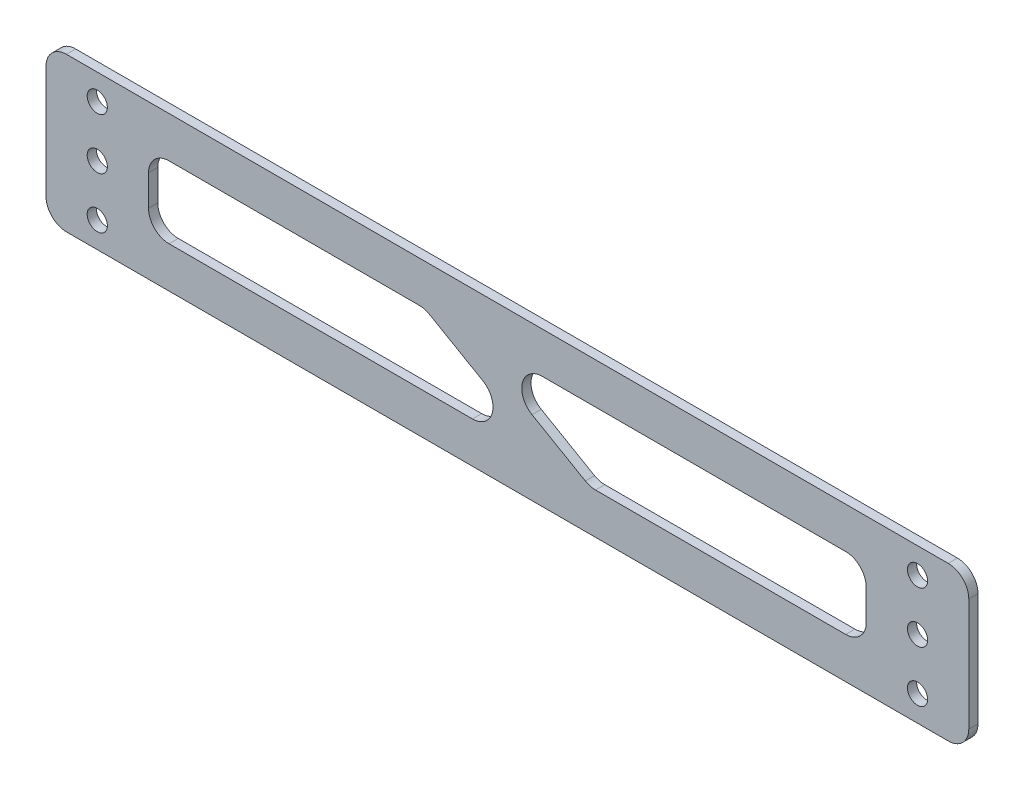
SolidWorks part; units mm, degrees
material "6061-T6 (SS)"
ref_plane "Front Plane" through (0, 0, 0) normal (0, 0, 1) x (1, 0, 0)
ref_plane "Top Plane" through (0, 0, 0) normal (0, 1, 0) x (1, 0, 0)
ref_plane "Right Plane" through (0, 0, 0) normal (1, 0, 0) x (0, 0, -1)
sketch "Sketch1" plane through (0, 0, 0) normal (0, 0, 1) x (1, 0, 0)
  line L1 (-12.7, 774.7) -> (49987.3, 774.7) construction
  line L2 (-7.62, 368.3) -> (210.82, 368.3) construction
  line L3 (-12.7, 1181.1) -> (-12.7, 368.3) construction
  line L4 (-7.62, 755.65) -> (210.82, 755.65)
  line L5 (-12.7, 760.73) -> (-12.7, 788.67)
  line L6 (-7.62, 793.75) -> (210.82, 793.75)
  line L7 (215.9, 760.73) -> (215.9, 788.67)
  line L8 (215.9, 1181.1) -> (215.9, 368.3) construction
  line L9 (17.78, 783.59) -> (79.7609, 783.59)
  line L10 (12.7, 1181.1) -> (12.7, 368.3) construction
  line L11 (190.5, 1181.1) -> (190.5, 368.3) construction
  line L12 (190.5, 778.51) -> (190.5, 770.89)
  line L13 (185.42, 765.81) -> (123.4391, 765.81)
  line L14 (12.7, 770.89) -> (12.7, 778.51)
  line L15 (82.3009, 782.9094) -> (95.4991, 775.2894)
  line L16 (107.7009, 774.1106) -> (120.8991, 766.4906)
  line L17 (81.1221, 783.59) -> (81.1221, -49216.41) construction
  line L18 (122.0779, 765.81) -> (122.0779, 50765.81) construction
  line L19 (101.6, 765.81) -> (101.6, 50765.81) construction
  line L20 (110.2409, 783.59) -> (185.42, 783.59)
  line L21 (92.9591, 765.81) -> (17.78, 765.81)
  arc A0 (210.82, 793.75) -> (215.9, 788.67) centre (210.82, 788.67) cw
  arc A1 (210.82, 755.65) -> (215.9, 760.73) centre (210.82, 760.73) ccw
  arc A2 (-12.7, 788.67) -> (-7.62, 793.75) centre (-7.62, 788.67) cw
  arc A3 (-7.62, 755.65) -> (-12.7, 760.73) centre (-7.62, 760.73) cw
  circle A4 centre (0, 762) radius 2.5
  circle A5 centre (0, 774.7) radius 2.5
  circle A6 centre (0, 787.4) radius 2.5
  circle A7 centre (203.2, 762) radius 2.5
  circle A8 centre (203.2, 774.7) radius 2.5
  circle A9 centre (203.2, 787.4) radius 2.5
  arc A10 (185.42, 783.59) -> (190.5, 778.51) centre (185.42, 778.51) cw
  arc A11 (190.5, 770.89) -> (185.42, 765.81) centre (185.42, 770.89) cw
  arc A12 (17.78, 765.81) -> (12.7, 770.89) centre (17.78, 770.89) cw
  arc A13 (17.78, 783.59) -> (12.7, 778.51) centre (17.78, 778.51) ccw
  arc A14 (120.8991, 766.4906) -> (123.4391, 765.81) centre (123.4391, 770.89) ccw
  arc A15 (107.7009, 774.1106) -> (110.2409, 783.59) centre (110.2409, 778.51) cw
  arc A16 (82.3009, 782.9094) -> (79.7609, 783.59) centre (79.7609, 778.51) ccw
  arc A17 (95.4991, 775.2894) -> (92.9591, 765.81) centre (92.9591, 770.89) cw
  point P14 (215.9, 793.75)
  point P17 (215.9, 755.65)
  point P22 (-12.7, 755.65)
  point P55 (190.5, 783.59)
  point P58 (190.5, 765.81)
  point P61 (12.7, 765.81)
  point P64 (12.7, 783.59)
  point P73 (122.0779, 765.81)
  point P76 (91.2821, 783.59)
  point P79 (81.1221, 783.59)
  point P82 (111.9179, 765.81)
  dimension "D4" = 5.08
  dimension "D7" = 5.08
  dimension "D12" = 5.08
  dimension "D1" = 406.4
  dimension "D2" = 38.1
  dimension "D3" = 19.05
  dimension "D5" = 10.16
  dimension "D6" = 10.16
  dimension "D8" = 5.08
  dimension "D9" = 30
  dimension "D10" = 20.4779
  dimension "D11" = 88.9
extrude "Boss-Extrude1" add sketch "Sketch1" along normal blind 2.286
sketch "Sketch2" [suppressed] plane through (0, 0, 0) normal (0, 0, 1) x (1, 0, 0)
  circle A0 centre (27.1191, 775.0388) radius 2.54
  circle A1 centre (68.5634, 775.0388) radius 2.54
  circle A2 centre (133.0475, 775.0388) radius 2.54
  circle A3 centre (171.352, 775.0388) radius 2.54
  point P8 (0, 0)
  point P9 (68.5634, 775.0388)
  dimension "D1" = 5.08
